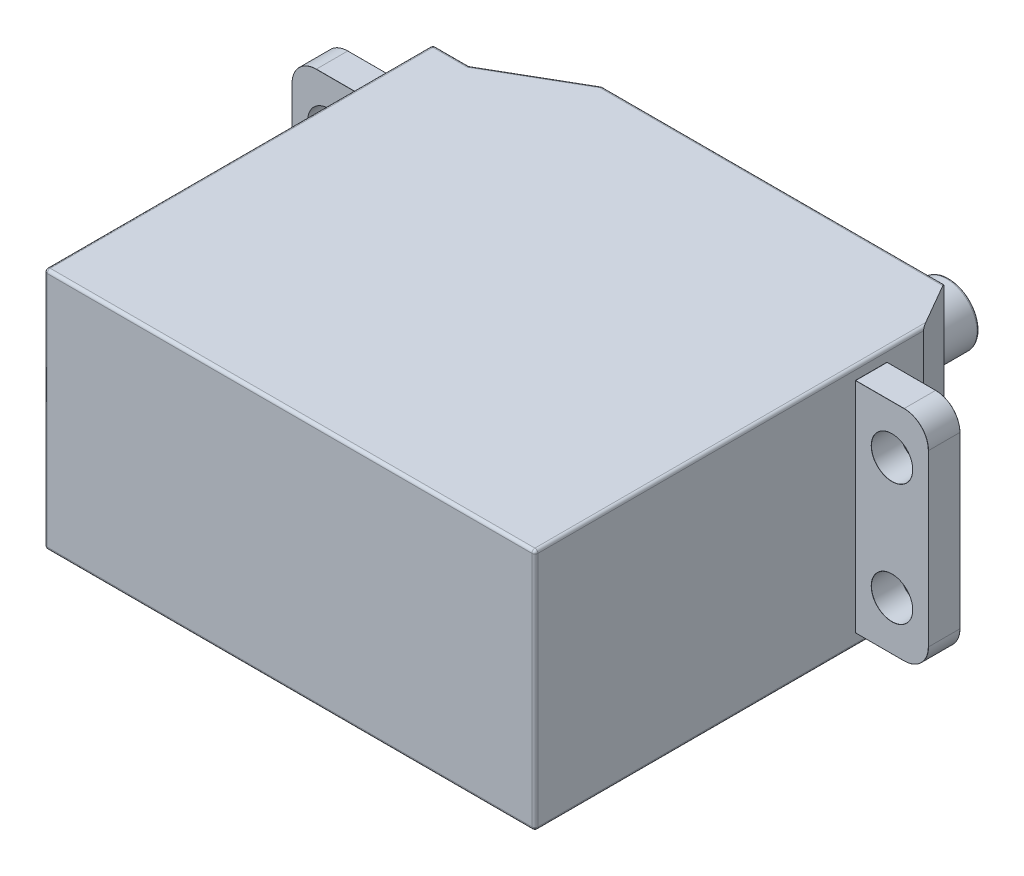
SolidWorks part; units mm, degrees
note: '?' marks a value the reader was unsure of.
ref_plane "前视" through (0, 0, 0) normal (0, 0, 1) x (1, 0, 0)
ref_plane "上视" through (0, 0, 0) normal (0, 1, 0) x (1, 0, 0)
ref_plane "右视" through (0, 0, 0) normal (1, 0, 0) x (0, 0, -1)
sketch "草图1" plane through (0, 0, 0) normal (0, 0, 1) x (1, 0, 0)
  line L1 (0, 0) -> (40.4, 0)
  line L2 (0, 0) -> (0, 20)
  line L3 (0, 20) -> (40.4, 20)
  line L4 (40.4, 0) -> (40.4, 20)
  dimension "D1" = 40.4
  dimension "D2" = 20
extrude "拉伸1" add sketch "草图1" along normal blind 32
sketch "草图3" plane through (0, 0, 0) normal (0, 1, 0) x (1, 0, 0)
  line L0 (3, 0) -> (9.9282, 4)
  line L1 (0, 0) -> (40.4, 0) construction
  line L2 (9.9282, 4) -> (38.0906, 4)
  line L3 (38.0906, 4) -> (40.4, 0)
  line L4 (3, 0) -> (40.4, 0)
  dimension "D1" = 4
  dimension "D2" = 30
  dimension "D3" = 60
  dimension "D4" = 3
extrude "拉伸2" add sketch "草图3" along normal blind 20
ref_plane "基准面1" through (0, 0, 3) normal (0, 0, 1) x (1, 0, 0)
sketch "草图4" plane through (0, 0, 3) normal (0, 0, 1) x (1, 0, 0)
  line L0 (0, 10) -> (18.3808, 10) construction
  line L1 (0, 20) -> (0, 0) construction
  line L2 (0, 19) -> (-4, 19)
  line L3 (-6, 17) -> (-6, 3)
  line L4 (0, 1) -> (-4, 1)
  line L5 (20.2, 20) -> (20.2, 10) construction
  line L6 (40.4, 20) -> (0, 20) construction
  line L7 (40.4, 1) -> (44.4, 1)
  line L8 (46.4, 17) -> (46.4, 3)
  line L9 (40.4, 19) -> (44.4, 19)
  line L10 (0, 19) -> (0, 1)
  line L11 (40.4, 19) -> (40.4, 1)
  circle A0 centre (-3, 15) radius 1.7
  arc A1 (-6, 17) -> (-4, 19) centre (-4, 17) cw
  arc A2 (-6, 3) -> (-4, 1) centre (-4, 3) ccw
  circle A3 centre (-3, 5) radius 1.7
  arc A4 (46.4, 3) -> (44.4, 1) centre (44.4, 3) cw
  circle A5 centre (43.4, 5) radius 1.7
  circle A6 centre (43.4, 15) radius 1.7
  arc A7 (46.4, 17) -> (44.4, 19) centre (44.4, 17) ccw
  point P11 (-6, 19)
  point P13 (-6, 10)
  dimension "D3" = 3
  dimension "D5" = 2
  dimension "D6" = 3.4
  dimension "D1" = 6
  dimension "D2" = 9
  dimension "D4" = 4
extrude "拉伸3" add sketch "草图4" along normal blind 2.6
sketch "草图5" plane through (0, 0, -4) normal (0, 0, -1) x (-1, 0, 0)
  line L0 (-38.0906, 20) -> (-9.9282, 20) construction
  line L1 (-40.4, 0) -> (-40.4, 20) construction
  line L3 (-36.4, 17) -> (-24.4, 17)
  line L6 (-24.6765, 17) -> (-37.5733, 17) [skipped]
  line L7 (-36.4, 3) -> (-24.4, 3)
  line L8 (-23.4, 4) -> (-23.4, 16)
  line L10 (-37.4, 16) -> (-37.4, 4)
  circle A0 centre (-30.4, 10) radius 7 construction
  arc A1 (-24.4, 17) -> (-23.4, 16) centre (-24.4, 16) cw
  arc A2 (-24.4, 3) -> (-23.4, 4) centre (-24.4, 4) ccw
  arc A3 (-37.4, 4) -> (-36.4, 3) centre (-36.4, 4) ccw
  arc A4 (-37.4, 16) -> (-36.4, 17) centre (-36.4, 16) cw
  dimension "D1" = 10
  dimension "D2" = 10
  dimension "D3" = 14
  dimension "D4" = 1
extrude "拉伸4" add sketch "草图5" along normal blind 0.1
ref_plane "基准面2" through (0, 10, 0) normal (0, 1, 0) x (-1, 0, 0)
fillet "圆角2" radius 0.25 15 edges at (0, 10, 0) (24.0094, 0, -4) (24.0094, 20, -4) (40.4, 20, 16) (40.4, 0, 16) (40.4, 10, 32) (0, 0, 16) (0, 20, 16) (20.2, 20, 32) (20.2, 0, 32) (0, 10, 32)
sketch "草图7" plane through (0, 10, 0) normal (0, 1, 0) x (-1, 0, 0)
  line L0 (0, 2.1792) -> (3, 2.9831)
  line L1 (4, 3) -> (0, 3) construction
  line L2 (0, 0.25) -> (0, 31.75) construction
  line L3 (0, 31.75) -> (0, 0.25) construction
  dimension "D1" = 15
  dimension "D2" = 3
rib "筋1" sketch "草图7" sketch "草图7" thickness 2 extrusion direction parallel to sketch draft on no parameters "D1"=2
sketch "草图8" plane through (0, 10, 0) normal (0, 1, 0) x (-1, 0, 0)
  line L0 (-43.4, 3) -> (-40.4, 2.1962)
  line L1 (-40.4, 3) -> (-44.4, 3) construction
  line L2 (-40.4, 0) -> (-40.4, 31.75) construction
  line L3 (-44.4, 3) -> (-40.4, 3) construction
  dimension "D1" = 15
  dimension "D2" = 3
rib "筋4" sketch "草图8" sketch "草图8" thickness 2 extrusion direction parallel to sketch draft on no parameters "D1"=2
chamfer "倒角2" distance 0.25 angle 30 4 edges at (-1.3, 15, 3) (-4.7, 5, 3) (45.1, 5, 3) (41.7, 15, 3)
sketch "Sketch1" plane through (0, 10, 0) normal (0, 1, 0) x (-1, 0, 0)
  line L0 (-30.4, -4.1) -> (-30.4, -12.1)
  line L1 (-24.4, -4.1) -> (-36.4, -4.1) construction
  line L2 (-30.4, -12.1) -> (-32.9, -12.1)
  line L3 (-32.9, -12.1) -> (-32.9, -5.1)
  line L4 (-35.4, -4.1) -> (-34.4, -5.1)
  line L5 (-30.4, -4.1) -> (-35.4, -4.1)
  line L6 (-32.9, -5.1) -> (-34.4, -5.1)
  line L7 (-30.4, -12.1) -> (-30.4, -1.0687) construction
revolve "Revolve2" add sketch "Sketch1" angle 360 about L7
ref_plane "Plane1" through (0, 0, -10) normal (0, 0, -1) x (-1, 0, 0)
fillet "Fillet2" radius 0.2 4 edges at (35.4, 10, -4.1) (26.4, 10, -5.1) (27.9, 10, -5.1) (27.9, 10, -12.1)
fillet "Fillet3" radius 0.01 52 edges at (0, 10, 5.6) (40.4, 9, 2.5981) (-5.4142, 18.4142, 5.6) (-5.4142, 1.5858, 5.6) (0, 11, 2.5896) (0, 19, 4.3) (-2, 19, 5.6) (-6, 10, 5.6) (-2, 1, 5.6) (0, 1, 4.3) (0, 15, 3) (-2, 19, 3) (-5.4142, 18.4142, 3) (-6, 10, 3) (-5.4142, 1.5858, 3) (-2, 1, 3) (0, 5, 3) (-1.5316, 11, 3) (-1.1557, 5, 3) (-1.1557, 15, 3) (-1.5316, 9, 3) (0, 9, 2.5896) (-1.5316, 11, 2.5896) (-3.0633, 10, 3) (-1.5316, 9, 2.5896) (0, 10, 2.1792) (45.1, 5, 5.6) (41.7, 15, 5.6) (45.8142, 18.4142, 3) (45.8142, 18.4142, 5.6) (45.8142, 1.5858, 3) (45.8142, 1.5858, 5.6) (40.4, 10, 5.6) (40.4, 1, 4.3) (42.4, 1, 3) (42.4, 1, 5.6) (42.4, 19, 3) (42.4, 19, 5.6) (40.4, 19, 4.3) (46.4, 10, 5.6) (46.4, 10, 3) (41.9, 9, 2.5981) (40.4, 10, 2.1962) (40.4, 11, 2.5981) (41.9, 11, 2.5981) (43.4, 10, 3) (41.9, 9, 3) (40.4, 5, 3) (40.4, 15, 3) (41.9, 11, 3) (41.5557, 15, 3) (41.5557, 5, 3)
sketch "Skizze1" plane through (0, 0, -4) normal (0, 0, -1) x (-1, 0, 0)
  line L2 (-17.8125, 18.3354) -> (-10.6502, 18.3354)
  line L3 (-17.8125, 1.6646) -> (-10.6502, 1.6646)
  line L4 (-10.6502, 18.3354) -> (-10.6502, 1.6646)
  line L5 (-17.8125, 18.3354) -> (-17.8125, 1.6646)
ref_axis "Axis1" through (43.4, 15, 5.59) along (0, 0, -1)?
ref_axis "Axis2" through (43.4, 5, 5.59) along (0, 0, -1)?
ref_axis "Axis3" through (-3, 15, 5.6) along (0, 0, -1)?
ref_axis "Axis4" through (-3, 5, 5.6) along (0, 0, -1)?
ref_axis "Axis5" through (30.4, 10, -11.9) along (0, 0, 1)?
